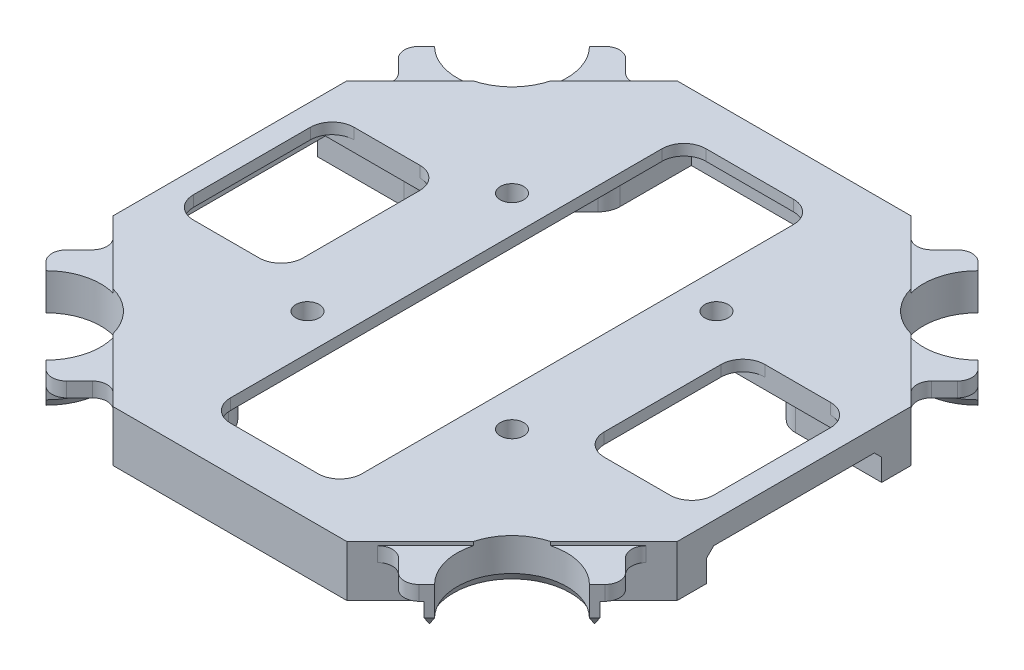
SolidWorks part; units mm, degrees
ref_plane "Front Plane" through (0, 0, 0) normal (0, 0, 1) x (1, 0, 0)
ref_plane "Top Plane" through (0, 0, 0) normal (0, 1, 0) x (1, 0, 0)
ref_plane "Right Plane" through (0, 0, 0) normal (1, 0, 0) x (0, 0, -1)
sketch "Sketch1" plane through (0, 0, 0) normal (0, 1, 0) x (1, 0, 0)
  line L1 (38.6274, 16) -> (16, 38.6274)
  line L2 (16, 38.6274) -> (-16, 38.6274)
  line L3 (-16, 38.6274) -> (-38.6274, 16)
  line L4 (-38.6274, 16) -> (-38.6274, -16)
  line L5 (-38.6274, -16) -> (-16, -38.6274)
  line L6 (-16, -38.6274) -> (16, -38.6274)
  line L7 (16, -38.6274) -> (38.6274, -16)
  line L8 (38.6274, -16) -> (38.6274, 16)
  circle A0 centre (0, 0) radius 38.6274 construction
  dimension "D1" = 32
extrude "Boss-Extrude1" add sketch "Sketch1" along normal blind 7
sketch "Sketch2" plane through (0, 7, 0) normal (0, 1, 0) x (1, 0, 0)
  line L0 (0, 0) -> (24.13, 24.13)
  line L2 (39.6865, 24.1299) -> (31.9082, 16.3516)
  line L4 (24.1302, 39.6863) -> (16.352, 31.9082)
  line L5 (16.352, 31.9082) -> (31.9082, 16.3516)
  line L18 (24.1302, 39.6863) -> (39.6865, 24.1299)
  line L19 (39.6863, -24.1302) -> (24.1299, -39.6865)
  line L20 (24.1299, -39.6865) -> (16.3516, -31.9082)
  line L21 (31.9082, -16.352) -> (16.3516, -31.9082)
  line L22 (39.6863, -24.1302) -> (31.9082, -16.352)
  line L23 (-24.1302, -39.6863) -> (-39.6865, -24.1299)
  line L24 (-39.6865, -24.1299) -> (-31.9082, -16.3516)
  line L25 (-16.352, -31.9082) -> (-31.9082, -16.3516)
  line L26 (-24.1302, -39.6863) -> (-16.352, -31.9082)
  line L27 (-39.6863, 24.1302) -> (-24.1299, 39.6865)
  line L28 (-24.1299, 39.6865) -> (-16.3516, 31.9082)
  line L29 (-31.9082, 16.352) -> (-16.3516, 31.9082)
  line L30 (-39.6863, 24.1302) -> (-31.9082, 16.352)
  point P22 (0, 0)
  point P26 (0.5304, 0.5304)
  line M6 (38.6274, 16) -> (16, 38.6274)
  line M8 (-16, 38.6274) -> (-38.6274, 16)
  line M10 (-38.6274, -16) -> (-16, -38.6274)
  line M12 (16, -38.6274) -> (38.6274, -16)
  dimension "D1" = 34.125
  dimension "D2" = 22
  dimension "D3" = 11.0001
  dimension "D4" = 4
extrude "Boss-Extrude2" add sketch "Sketch2" against normal blind 2.5 contours M8 | L2 L18 L4 M6 | L22 L24 M12 | L28 L27 M10 | L19 L20 L21 L22 region at (29.611, 7, -29.6109) region at (29.6109, 7, 29.611) region at (-29.611, 7, 29.6109) region at (-29.6109, 7, -29.611)
sketch "Sketch3" plane through (0, 4.5, 0) normal (0, -1, 0) x (1, 0, 0)
  line L1 (39.6863, 24.1302) -> (24.1299, 39.6865) construction
  circle A8 centre (31.9081, 31.9083) radius 11
  circle A9 centre (31.9083, -31.9081) radius 11
  circle A10 centre (-31.9081, -31.9083) radius 11
  circle A11 centre (-31.9083, 31.9081) radius 11
  point P13 (0, 0)
  line M3 (-35.092, 19.5354) -> (-19.5356, 35.0918)
  dimension "D1" = 4
extrude "Cut-Extrude1" cut sketch "Sketch3" along normal blind 10 contours M3 | A8 | A9 | A10 region at (-26.015, 4.5, 26.0147)
sketch "Sketch4" plane through (0, 4.5, 0) normal (0, -1, 0) x (-1, 0, 0)
  line L18 (39.6863, 24.1302) -> (24.1299, 39.6865) construction
  line L19 (37.9185, 25.8979) -> (37.2114, 26.605)
  line L20 (26.6048, 37.2116) -> (25.8976, 37.9187)
  line L21 (25.8979, -37.9185) -> (26.605, -37.2114)
  line L22 (37.2116, -26.6048) -> (37.9187, -25.8976)
  line L23 (-37.9185, -25.8979) -> (-37.2114, -26.605)
  line L24 (-26.6048, -37.2116) -> (-25.8976, -37.9187)
  line L25 (-25.8979, 37.9185) -> (-26.605, 37.2114)
  line L26 (-37.2116, 26.6048) -> (-37.9187, 25.8976)
  arc A16 (26.6048, 37.2116) -> (37.2114, 26.605) centre (31.9081, 31.9083) ccw
  arc A17 (25.8976, 37.9187) -> (37.9185, 25.8979) centre (31.9081, 31.9083) ccw
  arc A18 (37.9187, -25.8976) -> (25.8979, -37.9185) centre (31.9083, -31.9081) ccw
  arc A19 (37.2116, -26.6048) -> (26.605, -37.2114) centre (31.9083, -31.9081) ccw
  arc A20 (-25.8976, -37.9187) -> (-37.9185, -25.8979) centre (-31.9081, -31.9083) ccw
  arc A21 (-26.6048, -37.2116) -> (-37.2114, -26.605) centre (-31.9081, -31.9083) ccw
  arc A22 (-37.9187, 25.8976) -> (-25.8979, 37.9185) centre (-31.9083, 31.9081) ccw
  arc A23 (-37.2116, 26.6048) -> (-26.605, 37.2114) centre (-31.9083, 31.9081) ccw
  point P25 (0, 0)
extrude "Boss-Extrude3" add sketch "Sketch4" along normal blind 3
sketch "Sketch5" plane through (0, 4.5, 0) normal (0, -1, 0) x (-1, 0, 0)
  line L1 (37.2114, 26.605) -> (26.6048, 37.2116) construction
  circle A4 centre (31.9081, 31.9083) radius 7.5
  circle A5 centre (31.9083, -31.9081) radius 7.5
  circle A6 centre (-31.9081, -31.9083) radius 7.5
  circle A7 centre (-31.9083, 31.9081) radius 7.5
  point P13 (0, 0)
extrude "Cut-Extrude2" cut sketch "Sketch5" against normal blind 4
chamfer "Chamfer1" distance 1 distance2 0.5 7 edges at (37.565, 1.5, 26.2515) (25.8977, 1.5, 25.8979) (26.2512, 1.5, 37.5651) (26.6048, 1.5, 26.605) (-25.8979, 1.5, 25.8977) (-25.8977, 1.5, -25.8979) (25.8979, 1.5, -25.8977) first distance on face at (38.2721, 4.3333, 25.5444) first distance on face at (28.9029, 3, 28.9031) first distance on face at (25.5441, 4.3333, 38.2722) first distance on face at (29.2564, 4.25, 29.2566) first distance on face at (-28.9031, 3, 28.9029) first distance on face at (-28.9029, 3, -28.9031) first distance on face at (28.9031, 3, -28.9029)
fillet "Fillet1" radius 2 16 edges at (19.5356, 5.75, -35.0918) (24.1302, 5.75, -39.6863) (39.6865, 5.75, -24.1299) (35.092, 5.75, -19.5354) (35.0918, 5.75, 19.5356) (-24.1299, 5.75, -39.6865) (-19.5354, 5.75, -35.092) (-35.0918, 5.75, -19.5356) (-39.6863, 5.75, -24.1302) (-39.6865, 5.75, 24.1299) (-35.092, 5.75, 19.5354) (-19.5356, 5.75, 35.0918) (-24.1302, 5.75, 39.6863) (39.6863, 5.75, 24.1302) (24.1299, 5.75, 39.6865) (19.5354, 5.75, 35.092)
fillet "Fillet2" radius 2 8 edges at (-21.0376, 2.25, 33.5898) (-33.59, 2.25, 21.0374) (-33.5898, 2.25, -21.0376) (-21.0374, 2.25, -33.59) (33.59, 2.25, -21.0374) (21.0376, 2.25, -33.5898) (33.5898, 2.25, 21.0376) (21.0374, 2.25, 33.59)
sketch "Sketch6" plane through (0, 7, 0) normal (0, 1, 0) x (1, 0, 0)
  line L0 (-11, 26.5563) -> (-11, 36.5563)
  line L1 (26.5563, 11) -> (11, 26.5563)
  line L2 (11, 26.5563) -> (-11, 26.5563)
  line L3 (-11, 26.5563) -> (-26.5563, 11)
  line L4 (-26.5563, 11) -> (-26.5563, -11)
  line L5 (-26.5563, -11) -> (-11, -26.5563)
  line L6 (-11, -26.5563) -> (11, -26.5563)
  line L7 (11, -26.5563) -> (26.5563, -11)
  line L8 (26.5563, -11) -> (26.5563, 11)
  line L9 (11, 26.5563) -> (11, 36.5563)
  line L10 (11, 36.5563) -> (-11, 36.5563)
  line L11 (26.5563, -11) -> (36.5563, -11)
  line L12 (36.5563, -11) -> (36.5563, 11)
  line L13 (26.5563, 11) -> (36.5563, 11)
  line L14 (-11, -26.5563) -> (-11, -36.5563)
  line L15 (-11, -36.5563) -> (11, -36.5563)
  line L16 (11, -26.5563) -> (11, -36.5563)
  line L17 (-26.5563, 11) -> (-36.5563, 11)
  line L18 (-36.5563, 11) -> (-36.5563, -11)
  line L19 (-26.5563, -11) -> (-36.5563, -11)
  circle A0 centre (0, 0) radius 26.5563 construction
  point P28 (0, 0)
  dimension "D1" = 22
  dimension "D2" = 4
extrude "Cut-Extrude3" cut sketch "Sketch6" against normal blind 7 and the other way blind 5.5 from surface contours L7 L8 L1 L2 L3 L4 L5 L6 | L9 L10 L0 L2 | L19 L4 L17 L18 | L16 L6 L14 L15 | L13 L8 L11 L12 region at (0, 7, -31.5563) region at (0, 7, 0) region at (-31.5563, 7, 0) region at (31.5563, 7, 0) region at (0, 7, 31.5563) starting at face at (0, 0, 0)
sketch "Sketch7" plane through (0, 2, 0) normal (0, 1, 0) x (1, 0, 0)
  line L0 (0, 14) -> (0, 0)
  line L1 (0, 14) -> (-14, 14)
  circle A6 centre (-14, 14) radius 1.6
  circle A7 centre (14, 14) radius 1.6
  circle A8 centre (14, -14) radius 1.6
  circle A9 centre (-14, -14) radius 1.6
  point P13 (0, 0)
  point P17 (0, 0)
  dimension "D1" = 4
  dimension "D2" = 14
  dimension "D3" = 14
extrude "Cut-Extrude4" cut sketch "Sketch7" along normal blind 17 contours A9 | A9 | A6 | A6 | A6 | A7 | A7 | A8 | A8 region at (-15.5547, 2, -14) region at (14, 2, -14) region at (14, 2, 14) region at (-14, 2, 14)
sketch "Sketch8" plane through (0, 2, 0) normal (0, 1, 0) x (1, 0, 0)
  line L0 (35.6274, 2) -> (35.6274, -11)
  line L1 (26.5563, -11) -> (36.5563, -11) construction
  line L7 (0, -32.5563) -> (0, 32.5563) construction
  line L15 (0, 32.5563) -> (9, 32.5563)
  line L16 (9, 32.5563) -> (9, 20.5563)
  line L18 (0, 32.5563) -> (-9, 32.5563)
  line L19 (-9, 32.5563) -> (-9, 18.5563)
  line L27 (0, -32.5563) -> (-9, -32.5563)
  line L28 (-9, -32.5563) -> (-9, -22.5563)
  line L30 (0, -32.5563) -> (9, -32.5563)
  line L31 (9, -32.5563) -> (9, -20.5563)
  line L32 (-9, 18.5563) -> (-9, -22.5563)
  line L33 (9, 20.5563) -> (9, -20.5563)
  line L35 (35.6274, 2) -> (35.6274, 11)
  line L36 (35.6274, 11) -> (20.6274, 11)
  line L37 (-38.6274, 16) -> (-38.6274, -16) construction
  line L45 (35.6274, -11) -> (20.6274, -11)
  line L46 (20.6274, -11) -> (20.6274, 11)
  line L47 (-20.6274, -11) -> (-20.6274, 11)
  line L48 (-35.6274, -11) -> (-20.6274, -11)
  line L49 (-35.6274, 11) -> (-20.6274, 11)
  line L50 (-35.6274, 2) -> (-35.6274, 11)
  line L51 (-35.6274, 2) -> (-35.6274, -11)
  point P38 (0, 0)
  dimension "D1" = 3
  dimension "D2" = 15
extrude "Cut-Extrude5" cut sketch "Sketch8" along normal blind 12 contours L27 L7 L18 L19 L32 L28 | L7 L30 L31 L33 L16 L15 | L46 L45 L0 L35 L36 | L47 L49 L50 L51 L48 region at (28.1274, 2, 0) region at (-4.5, 2, 0) region at (4.5, 2, 0)
fillet "Fillet4" radius 3 4 edges at (-9, 6.25, 32.5563) (9, 6.25, 32.5563) (9, 6.25, -32.5563) (-9, 6.25, -32.5563)
fillet "Fillet5" radius 3 8 edges at (-35.6274, 6.25, 11) (-20.6274, 6.25, 11) (-20.6274, 6.25, -11) (-35.6274, 6.25, -11) (35.6274, 6.25, 11) (20.6274, 6.25, 11) (20.6274, 6.25, -11) (35.6274, 6.25, -11)
sketch "Sketch9" plane through (0, 2, 0) normal (0, 1, 0) x (1, 0, 0)
  line L0 (-28.2132, 11) -> (-14, 11)
  line L1 (-28.2132, 11) -> (-22.6888, 16.5244)
  line L2 (-11, 28.2132) -> (-11, 14)
  line L3 (-16.3881, 22.8251) -> (-11, 28.2132)
  line L4 (-22.6888, 16.5244) -> (-21.0649, 16.4915)
  line L5 (-11, 26.5563) -> (-26.5563, 11) construction
  line L6 (-16.3881, 22.8251) -> (-16.2063, 21.3501)
  line L7 (-11, 26.5563) -> (-26.5563, 11) construction
  line L8 (-16.2063, 21.3501) -> (-21.0649, 16.4915)
  line L30 (11, 28.2132) -> (11, 14)
  line L31 (11, 28.2132) -> (16.5244, 22.6888)
  line L32 (28.2132, 11) -> (14, 11)
  line L33 (22.8251, 16.3881) -> (28.2132, 11)
  line L34 (16.5244, 22.6888) -> (16.4915, 21.0649)
  line L35 (22.8251, 16.3881) -> (21.3501, 16.2063)
  line L36 (21.3501, 16.2063) -> (16.4915, 21.0649)
  line L37 (28.2132, -11) -> (14, -11)
  line L38 (28.2132, -11) -> (22.6888, -16.5244)
  line L39 (11, -28.2132) -> (11, -14)
  line L40 (16.3881, -22.8251) -> (11, -28.2132)
  line L41 (22.6888, -16.5244) -> (21.0649, -16.4915)
  line L42 (16.3881, -22.8251) -> (16.2063, -21.3501)
  line L43 (16.2063, -21.3501) -> (21.0649, -16.4915)
  line L44 (-11, -28.2132) -> (-11, -14)
  line L45 (-11, -28.2132) -> (-16.5244, -22.6888)
  line L46 (-28.2132, -11) -> (-14, -11)
  line L47 (-22.8251, -16.3881) -> (-28.2132, -11)
  line L48 (-16.5244, -22.6888) -> (-16.4915, -21.0649)
  line L49 (-22.8251, -16.3881) -> (-21.3501, -16.2063)
  line L50 (-21.3501, -16.2063) -> (-16.4915, -21.0649)
  arc A1 (-14, 11) -> (-11, 14) centre (-14, 14) ccw
  circle A2 centre (-14, 14) radius 1.6
  arc A10 (11, 14) -> (14, 11) centre (14, 14) ccw
  circle A11 centre (14, 14) radius 1.6
  arc A12 (14, -11) -> (11, -14) centre (14, -14) ccw
  circle A13 centre (14, -14) radius 1.6
  arc A14 (-11, -14) -> (-14, -11) centre (-14, -14) ccw
  circle A15 centre (-14, -14) radius 1.6
  point P49 (0.1363, -0.0701)
  point P51 (0, 0)
  dimension "D1" = 4
extrude "Boss-Extrude6" add sketch "Sketch9" against normal blind 1.5 from surface starting at face at (-14, 5.5, 15.6)
sketch "Sketch12" plane through (0, 7, 0) normal (0, 1, 0) x (1, 0, 0)
  line L0 (-36.5563, 0) -> (-36.5563, 12)
  line L1 (-36.5563, 11) -> (-36.5563, -11) construction
  line L2 (-36.5563, 12) -> (-12, 12)
  line L4 (-12, -12) -> (-36.5563, -12)
  line L5 (-36.5563, 0) -> (-36.5563, -12)
  line L6 (0, 36.5563) -> (12, 36.5563)
  line L7 (12, 36.5563) -> (12, 12)
  line L9 (-12, 12) -> (-12, 36.5563)
  line L10 (0, 36.5563) -> (-12, 36.5563)
  line L11 (36.5563, 0) -> (36.5563, -12)
  line L12 (36.5563, -12) -> (12, -12)
  line L14 (12, 12) -> (36.5563, 12)
  line L15 (36.5563, 0) -> (36.5563, 12)
  line L16 (0, -36.5563) -> (-12, -36.5563)
  line L17 (-12, -36.5563) -> (-12, -12)
  line L19 (12, -12) -> (12, -36.5563)
  line L20 (0, -36.5563) -> (12, -36.5563)
  line L21 (-11, 14) -> (-11, 36.5563) construction
  line L22 (11, 36.5563) -> (-11, 36.5563) construction
  point P25 (0, 0)
  dimension "D1" = 12
  dimension "D2" = 24
  dimension "D4" = 1
  dimension "D5" = 0
  dimension "D3" = 4
extrude "Cut-Extrude6" cut sketch "Sketch12" along normal up to surface (4 mm away) from surface up to face at (-15.4838, 4, -15.4838) starting at face at (0, 0, 0)
fillet "Fillet6" radius 3 8 edges at (-12, 2, 25.5563) (-25.5563, 2, 12) (12, 2, 25.5563) (25.5563, 2, 12) (12, 2, -25.5563) (25.5563, 2, -12) (-12, 2, -25.5563) (-25.5563, 2, -12)
sketch "Sketch14" plane through (0, 7, 0) normal (0, 1, 0) x (1, 0, 0)
  line L1 (38.6274, 16) -> (16, 38.6274)
  line L2 (16, 38.6274) -> (-16, 38.6274)
  line L3 (-16, 38.6274) -> (-38.6274, 16)
  line L4 (-38.6274, 16) -> (-38.6274, -16)
  line L5 (-38.6274, -16) -> (-16, -38.6274)
  line L6 (-16, -38.6274) -> (16, -38.6274)
  line L7 (16, -38.6274) -> (38.6274, -16)
  line L8 (38.6274, -16) -> (38.6274, 16)
  circle A0 centre (0, 0) radius 38.6274 construction
  circle A1 centre (0, 0) radius 70.1465
extrude "Cut-Extrude8" cut sketch "Sketch14" against normal blind 0.5
sketch "Sketch15" plane through (0, 4, 0) normal (0, -1, 0) x (1, 0, 0)
  line L0 (-36.5563, 12) -> (-36.5563, -12)
  line L1 (-36.5563, -12) -> (-38.6274, -12)
  line L2 (-38.6274, -16) -> (-38.6274, 16) construction
  line L3 (-38.6274, -12) -> (-38.6274, 12)
  line L4 (-38.6274, 12) -> (-36.5563, 12)
  line L5 (36.5563, 12) -> (38.6274, 12)
  line L6 (38.6274, 16) -> (38.6274, -16) construction
  line L7 (36.5563, 12) -> (36.5563, -12)
  line L8 (36.5563, -12) -> (38.6274, -12)
  line L9 (38.6274, -12) -> (38.6274, 12)
extrude "Cut-Extrude10" cut sketch "Sketch15" along normal up to surface (4 mm away) up to face at (0, 0, 0)
chamfer "Chamfer2" distance 1 angle 45 20 edges at (12, 4, 31.6777) (12.2284, 4, 25.6509) (18.7782, 4, 18.7782) (25.6509, 4, 12.2284) (32.7132, 4, 12) (12, 4, -31.6777) (12.2284, 4, -25.6509) (18.7782, 4, -18.7782) (25.6509, 4, -12.2284) (32.7132, 4, -12) (-12, 4, -31.6777) (-12.2284, 4, -25.6509) (-18.7782, 4, -18.7782) (-25.6509, 4, -12.2284) (-32.7132, 4, -12) (-12, 4, 31.6777) (-12.2284, 4, 25.6509) (-18.7782, 4, 18.7782) (-25.6509, 4, 12.2284) (-32.7132, 4, 12)
